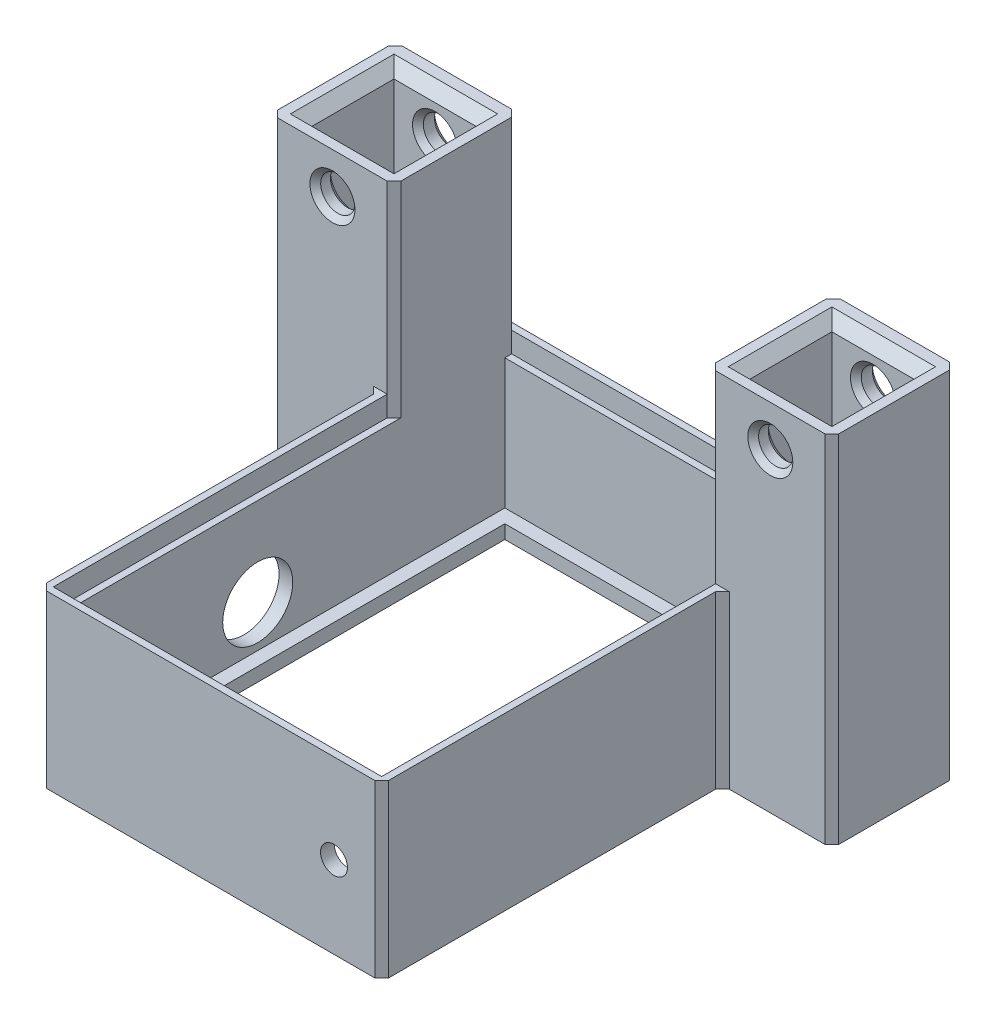
SolidWorks part; units mm, degrees
ref_plane "Front Plane" through (0, 0, 0) normal (0, 0, 1) x (1, 0, 0)
ref_plane "Top Plane" through (0, 0, 0) normal (0, 1, 0) x (1, 0, 0)
ref_plane "Right Plane" through (0, 0, 0) normal (1, 0, 0) x (0, 0, -1)
sketch "Sketch3" plane through (0, 0, 0) normal (0, 1, 0) x (-1, 0, 0)
  line L1 (0, 0) -> (63.5, 0)
  line L2 (0, 0) -> (0, 86.36)
  line L3 (0, 86.36) -> (63.5, 86.36)
  line L4 (63.5, 0) -> (63.5, 86.36)
  dimension "D1" = 86.36
  dimension "D2" = 63.5
extrude "Boss-Extrude2" add sketch "Sketch3" against normal blind 31.75
sketch "Sketch4" plane through (0, -31.75, 0) normal (0, -1, 0) x (1, 0, 0)
  line L1 (-2.54, 83.82) -> (-60.96, 83.82)
  line L2 (-2.54, 83.82) -> (-2.54, 2.54)
  line L3 (-2.54, 2.54) -> (-60.96, 2.54)
  line L4 (-60.96, 83.82) -> (-60.96, 2.54)
  line L8 (-63.5, 86.36) -> (0, 86.36) construction
  line L9 (0, 0) -> (-63.5, 0) construction
  line L10 (0, 86.36) -> (0, 0) construction
  line L11 (-63.5, 0) -> (-63.5, 86.36) construction
  dimension "D1" = 2.54
  dimension "D2" = 2.54
  dimension "D3" = 2.54
  dimension "D4" = 2.54
extrude "Cut-Extrude2" cut sketch "Sketch4" against normal offset from surface (27.94 mm away) 3.81 up to face at (-31.75, 0, 43.18)
sketch "Sketch5" plane through (-63.5, 0, 0) normal (1, 0, 0) x (0, 0, -1)
  line L5 (0, -31.75) -> (-86.36, -31.75) construction
  line L8 (0, -31.75) -> (0, 0) construction
  circle A0 centre (-48.41, -20.17) radius 6.5
  dimension "D1" = 13
  dimension "D2" = 5.08
  dimension "D3" = 41.91
extrude "Cut-Extrude3" cut sketch "Sketch5" along normal up to next
sketch "Sketch6" plane through (-63.5, 0, 0) normal (-1, 0, 0) x (0, 0, 1)
  line L0 (46.54, 0) -> (46.54, 36.83)
  line L1 (46.54, 36.83) -> (0, 36.83)
  line L2 (0, 36.83) -> (0, 34.29)
  line L3 (0, 34.29) -> (44, 34.29)
  line L4 (44, 34.29) -> (44, 0)
  line L5 (0, 0) -> (86.36, 0) construction
  line L6 (44, 0) -> (46.54, 0)
  line L7 (0, -31.75) -> (0, 0) construction
  dimension "D1" = 44
  dimension "D2" = 34.29
  dimension "D3" = 2.54
  dimension "D4" = 2.54
extrude "Motor Mounting Shape" add sketch "Sketch6" against normal up to surface (63.5 mm away) up to face at (0, -15.875, 43.18)
sketch "Sketch8" plane through (0, 36.83, 0) normal (0, 1, 0) x (1, 0, 0)
  line L0 (-47.25, -38.77) -> (-16.25, -7.77) construction
  line L1 (-16.25, -38.77) -> (-47.25, -7.77) construction
  line L2 (-47.25, -38.77) -> (-47.25, -7.77) construction
  line L3 (-47.25, -7.77) -> (-16.25, -7.77) construction
  line L4 (-31.75, -46.54) -> (-31.75, 0) construction
  line L5 (0, -46.54) -> (-63.5, -46.54) construction
  line L6 (0, 0) -> (-63.5, 0) construction
  line L7 (-40.64, 0) -> (-22.86, 0)
  line L8 (-22.86, 0) -> (-22.86, -23.27)
  line L9 (-40.64, -23.27) -> (-40.64, 0)
  circle A1 centre (-47.25, -7.77) radius 1.6
  circle A2 centre (-16.25, -7.77) radius 1.6
  circle A3 centre (-16.25, -38.77) radius 1.6
  circle A4 centre (-47.25, -38.77) radius 1.6
  arc A6 (-40.64, -23.27) -> (-22.86, -23.27) centre (-31.75, -23.27) ccw
  point P10 (-31.75, -23.27)
  dimension "D2" = 3.2
  dimension "D3" = 8.89
  dimension "D1" = 31
extrude "Motor-Mounting-Holes" cut sketch "Sketch8" against normal up to next
sketch "Sketch13" plane through (0, 0, 0) normal (0, 1, 0) x (1, 0, 0)
  line L0 (-31.75, -85.09) -> (-31.75, -86.36) construction
  line L1 (-62.23, -1.27) -> (-1.27, -1.27)
  line L2 (-62.23, -1.27) -> (-62.23, -85.09)
  line L3 (-62.23, -85.09) -> (-1.27, -85.09)
  line L4 (-1.27, -1.27) -> (-1.27, -85.09)
  line L5 (-63.5, -86.36) -> (0, -86.36) construction
  line L6 (-63.5, -46.54) -> (-63.5, -86.36) construction
  line L7 (0, 0) -> (-63.5, 0) construction
  dimension "D1" = 1.27
  dimension "D2" = 1.27
  dimension "D3" = 1.27
extrude "Cut-Extrude7" cut sketch "Sketch13" against normal up to surface (3.81 mm away) up to face at (-31.75, -3.81, 43.18)
sketch "Sketch9" plane through (0, -31.75, 0) normal (0, -1, 0) x (1, 0, 0)
  line L0 (1.27, 23.114) -> (-2.54, 23.114)
  line L1 (1.27, 0) -> (20.32, 0)
  line L2 (1.27, 4.064) -> (1.27, 19.304)
  line L3 (1.27, 23.114) -> (20.32, 23.114)
  line L5 (20.32, 23.114) -> (20.32, 0)
  line L6 (1.27, 19.304) -> (16.51, 19.304)
  line L7 (16.51, 19.304) -> (16.51, 4.064)
  line L8 (16.51, 4.064) -> (1.27, 4.064)
  line L10 (-2.54, 23.114) -> (-2.54, 0)
  line L11 (-31.75, 86.36) -> (-31.75, 0) construction
  line L12 (-2.54, 0) -> (1.27, 0)
  line L13 (1.27, 19.304) -> (1.27, 4.064)
  line L14 (0, 0) -> (-63.5, 0) construction
  line L15 (-63.5, 86.36) -> (0, 86.36) construction
  line L16 (-80.01, 19.304) -> (-80.01, 4.064)
  line L17 (-80.01, 4.064) -> (-64.77, 4.064)
  line L18 (-64.77, 4.064) -> (-64.77, 19.304)
  line L19 (-64.77, 19.304) -> (-80.01, 19.304)
  line L20 (-60.96, 0) -> (-64.77, 0)
  line L21 (-60.96, 23.114) -> (-60.96, 0)
  line L22 (-64.77, 23.114) -> (-60.96, 23.114)
  line L23 (-64.77, 23.114) -> (-83.82, 23.114)
  line L24 (-83.82, 23.114) -> (-83.82, 0)
  line L25 (-64.77, 0) -> (-83.82, 0)
  line L26 (-2.54, 2.54) -> (-2.54, 83.82) construction
  point P11 (-2.54, 39.624)
  point P28 (0, 0)
  point P30 (0, 0)
  point P31 (0, 0)
  point P32 (-64.77, 16.51)
  point P33 (0, 0)
  point P34 (-2.54, 0)
  dimension "D1" = 3.81
  dimension "D2" = 4.064
  dimension "D3" = 3.81
  dimension "D4" = 15.24
  dimension "D5" = 3.81
  dimension "D6" = 3.81
  dimension "D8" = 33.02
extrude "Boss-Extrude3" add sketch "Sketch9" against normal blind 66 contours L1 L5 L3 L0 L10 L12 | L13 L8 L7 L6 | L20 L25 L24 L23 L22 L21 | L16 L17 L18 L19
chamfer "Chamfer1" distance 2 angle 45 8 edges at (-64.77, 34.25, 11.684) (-72.39, 34.25, 4.064) (-80.01, 34.25, 11.684) (-72.39, 34.25, 19.304) (8.89, 34.25, 4.064) (1.27, 34.25, 11.684) (16.51, 34.25, 11.684) (8.89, 34.25, 19.304)
sketch "Sketch11" plane through (0, 0, 0) normal (1, 0, 0) x (0, 0, -1)
  line L0 (-44, 0) -> (-44, 34.29)
  line L1 (-44, 34.29) -> (0, 34.29)
  line L2 (0, 34.29) -> (0, 51.5993)
  line L3 (0, 51.5993) -> (-81.1962, 51.5993)
  line L4 (-81.1962, 51.5993) -> (-81.1962, 0)
  line L5 (-81.1962, 0) -> (-44, 0)
extrude "Cut-Extrude5" cut sketch "Sketch11" against normal through all
sketch "Sketch12" plane through (0, 0, 23.114) normal (0, 0, 1) x (1, 0, 0)
  line L0 (20.32, -31.75) -> (0, -31.75) construction
  line L1 (-60.96, 34.25) -> (-60.96, -3.81) construction
  line L2 (-2.54, 34.25) -> (-2.54, -3.81) construction
  circle A0 centre (8.89, 26.67) radius 3.175
  circle A1 centre (-72.39, 26.67) radius 3.175
  dimension "D1" = 6.35
  dimension "D3" = 6.35
  dimension "D2" = 58.42
  dimension "D4" = 11.43
  dimension "D5" = 11.43
extrude "Cut-Extrude6" cut sketch "Sketch12" against normal through all
chamfer "Chamfer2" distance 1 angle 45 8 edges at (12.065, 26.67, 23.114) (5.715, 26.67, 19.304) (12.065, 26.67, 4.064) (12.065, 26.67, 0) (-69.215, 26.67, 0) (-75.565, 26.67, 4.064) (-69.215, 26.67, 19.304) (-69.215, 26.67, 23.114)
sketch "Sketch14" plane through (0, -31.75, 0) normal (0, -1, 0) x (1, 0, 0)
  line L1 (-58.42, 81.28) -> (-5.08, 81.28)
  line L2 (-58.42, 81.28) -> (-58.42, 5.08)
  line L3 (-58.42, 5.08) -> (-5.08, 5.08)
  line L4 (-5.08, 81.28) -> (-5.08, 5.08)
  line L5 (-2.54, 83.82) -> (-60.96, 83.82) construction
  line L7 (-2.54, 2.54) -> (-2.54, 83.82) construction
  line L10 (-60.96, 83.82) -> (-2.54, 83.82)
  line L11 (-60.96, 83.82) -> (-60.96, 2.54)
  line L12 (-60.96, 2.54) -> (-2.54, 2.54)
  line L13 (-2.54, 83.82) -> (-2.54, 2.54)
  dimension "D1" = 2.54
  dimension "D2" = 2.54
  dimension "D3" = 2.54
  dimension "D4" = 2.54
extrude "Boss-Extrude5" add sketch "Sketch14" along normal blind 2.54 from offset 3.81 offset against normal yes
sketch "Sketch15" plane through (0, 0, 86.36) normal (0, 0, 1) x (1, 0, 0)
  line L0 (-63.5, -31.75) -> (0, -31.75) construction
  line L1 (0, -31.75) -> (0, 0) construction
  circle A0 centre (-8.85, -16.55) radius 2.5
  dimension "D1" = 5
  dimension "D2" = 12.7
  dimension "D3" = 6.35
extrude "Cut-Extrude8" cut sketch "Sketch15" against normal up to next
chamfer "Chamfer3" distance 1.27 angle 45 12 edges at (-63.5, -15.875, 86.36) (0, -15.875, 86.36) (0, -15.875, 23.114) (20.32, 1.25, 23.114) (20.32, 1.25, 0) (-2.54, 15.22, 23.114) (-2.54, 17.125, 0) (-60.96, 15.22, 23.114) (-60.96, 17.125, 0) (-83.82, 1.25, 0) (-83.82, 1.25, 23.114) (-63.5, -15.875, 23.114)
